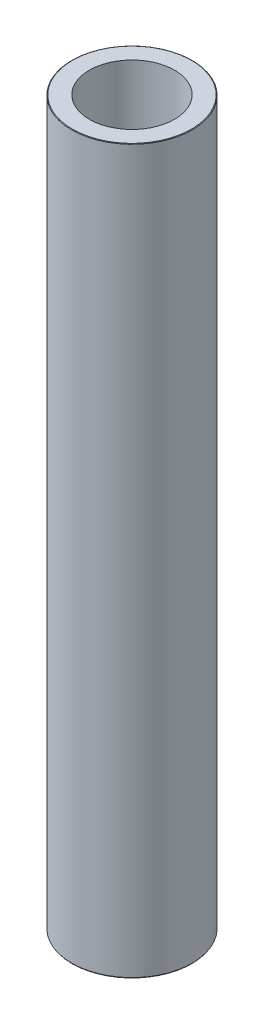
SolidWorks part; units mm, degrees
ref_plane "Front Plane" through (0, 0, 0) normal (0, 0, 1) x (1, 0, 0)
ref_plane "Top Plane" through (0, 0, 0) normal (0, 1, 0) x (1, 0, 0)
ref_plane "Right Plane" through (0, 0, 0) normal (1, 0, 0) x (0, 0, -1)
sketch "Sketch1" plane through (0, 0, 0) normal (0, 1, 0) x (1, 0, 0)
  circle A0 centre (0, 0) radius 50
  dimension "SHAFT_OD" = 100
extrude "Boss-Extrude1" add sketch "Sketch1" along normal blind 600
sketch "Sketch2" plane through (0, 0, 0) normal (0, 1, 0) x (1, 0, 0)
  circle A0 centre (0, 0) radius 35.3533
  dimension "BORE_D" = 70.7066
extrude "Cut-Extrude1" cut sketch "Sketch2" along normal through all
chamfer "Chamfer1" distance 0.3088 angle 60 2 edges at (0, 600, 50) (0, 0, 50) first distance on face at (0, 600, 50) first distance on face at (0, 0, 35.3533)
